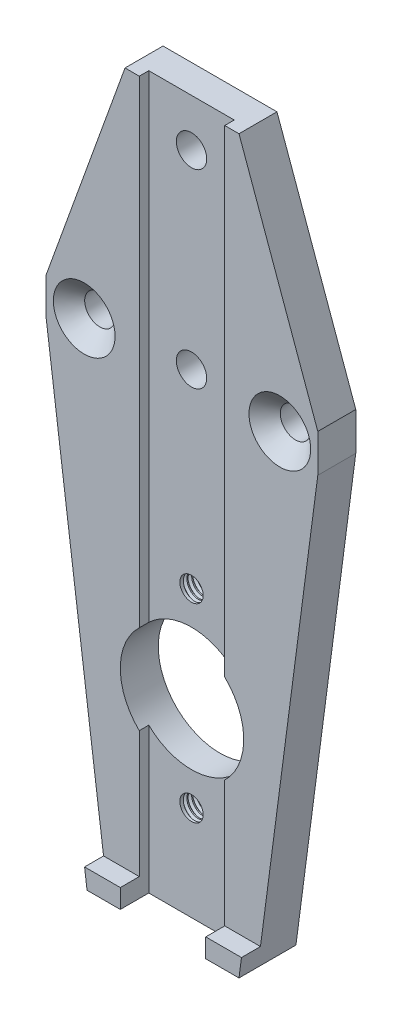
SolidWorks part; units mm, degrees
ref_plane "前视基准面" through (0, 0, 0) normal (0, 0, 1) x (1, 0, 0)
ref_plane "上视基准面" through (0, 0, 0) normal (0, 1, 0) x (1, 0, 0)
ref_plane "右视基准面" through (0, 0, 0) normal (1, 0, 0) x (0, 0, -1)
sketch "Model" plane through (0, 0, 0) normal (0, 0, 1) x (1, 0, 0)
  line L0 (-22.9666, -11.0807) -> (-22.9666, 4.2289)
  line L1 (-22.9666, -9.0807) -> (-26.7597, -9.0807)
  line L2 (-13.9666, -11.0807) -> (-13.9666, 4.2289)
  line L3 (-10.4666, -11.0807) -> (-26.4666, -11.0807)
  line L4 (-13.9666, -9.0807) -> (-10.1736, -9.0807)
  line L5 (-4.1666, 36.9193) -> (-4.1666, 40.9193)
  line L6 (-10.4666, -11.0807) -> (-4.1666, 36.9193)
  line L7 (-32.7666, 36.9193) -> (-32.7666, 40.9193)
  line L8 (-22.9666, 13.6097) -> (-22.9666, 63.9193)
  line L9 (-26.4666, -11.0807) -> (-32.7666, 36.9193)
  line L10 (-13.9666, 13.6097) -> (-13.9666, 63.9193)
  line L11 (-24.4666, 63.9193) -> (-12.4666, 63.9193)
  line L12 (-12.4666, 63.9193) -> (-4.1666, 40.9193)
  line L13 (-24.4666, 63.9193) -> (-32.7666, 40.9193)
  circle A0 centre (-18.4666, 8.9193) radius 6.5
  circle A1 centre (-8.1666, 38.9193) radius 1.6
  circle A2 centre (-18.4666, 38.9193) radius 1.6
  circle A3 centre (-28.7666, 38.9193) radius 1.6
  circle A4 centre (-18.4666, 58.9193) radius 1.6
  circle A5 centre (-8.1666, 38.9193) radius 3.25
  circle A6 centre (-28.7666, 38.9193) radius 3.25
  circle A7 centre (-18.4666, 18.9193) radius 1.2294
  arc A8 (-18.4666, 17.4193) -> (-19.9438, 18.6588) centre (-18.4666, 18.9193) ccw
  circle A9 centre (-18.4666, -1.0807) radius 1.2294
  arc A10 (-18.4666, -2.5807) -> (-19.9438, -1.3412) centre (-18.4666, -1.0807) ccw
extrude "凸台-拉伸1" add sketch "Model" along normal blind 3 contours A0 L10 L11 L8 A7 A4 A2 | A0 L0 L3 L2 A9 region at (-18.4666, -4.1536, 0) region at (-22.4556, 38.7645, 0)
extrude "凸台-拉伸2" add sketch "Model<3>" along normal blind 4 contours A0 L8 L11 L13 L7 L9 L1 L0 A6 | A0 L2 L4 L6 L5 L12 L11 L10 A5 | A6 A3 | A3 | A5 A1 | A1 | L9 L3 L0 L1 | L3 L6 L4 L2 region at (-24.783, -10.0687, 0) region at (-26.5297, 27.523, 0) region at (-12.1502, -10.0687, 0) region at (-10.4036, 27.523, 0) region at (-8.1666, 38.9193, 0) region at (-28.7666, 38.9193, 0) region at (-11.3247, 38.9193, 0) region at (-31.9247, 38.9193, 0)
sketch "Model<3>" plane through (0, 0, 0) normal (0, 0, 1) x (1, 0, 0) same geometry as "Model"
extrude "凸台-拉伸3" add sketch "Model<4>" along normal blind 6 contours L9 L3 L0 L1 | L3 L6 L4 L2 region at (-24.783, -10.0687, 0) region at (-12.1502, -10.0687, 0)
sketch "Model<4>" plane through (0, 0, 0) normal (0, 0, 1) x (1, 0, 0) same geometry as "Model"
sketch "草图2" plane through (0, 0, 4) normal (0, 0, 1) x (1, 0, 0)
  point P0 (-8.1666, 38.9193)
  point P2 (-28.7666, 38.9193)
hole_wizard "打孔尺寸(%根据)内六角花形半沉头螺钉的类型1" positions "3D草图1" profile "草图3" countersink size "M6" standard "GB" end condition up to next
sketch3d "3D草图1"
  point P0 (-28.7666, 38.9193, 4)
  point P3 (-8.1666, 38.9193, 4)
sketch "草图3" plane through (-28.7666, 38.9193, 4) normal (1, 0, 0) x (0, -1, 0)
  line L0 (0, 0) -> (0, 4)
  line L1 (0, 4) -> (1.6, 4)
  line L2 (1.6, 4) -> (1.6, 1.65)
  line L3 (1.6, 1.65) -> (3.25, 0)
  line L5 (3.25, 0) -> (0, 0)
  line L6 (-1.6, 1.65) -> (-3.25, 0) construction
  line L11 (0, -6.35) -> (0, 107.95) construction
  dimension "通孔孔直径" = 3.2
  dimension "通孔孔深度" = 4
  dimension "近端锥形沉头孔直径" = 6.5
  dimension "近端锥形沉头孔角度" = 90
thread "螺纹线4" pitch 0.5 method cut profile "螺纹线轮廓4" start angle 0, offset 0, length 0, pitch 0.5, diameter 2.4587
ref_plane "基准面7" through (-17.2373, 18.9193, 0) normal (0, -1, 0) x (1, 0, 0)
sketch "螺纹线轮廓4" plane through (-17.2373, 18.9193, 0) normal (0, -1, 0) x (1, 0, 0)
  line L0 (0, 0) -> (0, 0.5) construction
  line L1 (0, 0) -> (0.2706, 0.1562)
  line L2 (0.2706, 0.1562) -> (0.2706, 0.2187)
  line L3 (0.2706, 0.2187) -> (0, 0.375)
  line L4 (0.2706, 0.1875) -> (0, 0.1875) construction
  line L11 (0, 0) -> (0, 0.375)
  point P2 (0, 0)
  dimension "Pitch" = 0.5
  dimension "Profile_Angle" = 60
  dimension "Profile_Land" = 0.0625
  dimension "Profile_Height" = 0.2706
thread "螺纹线5" pitch 0.5 method cut profile "螺纹线轮廓5" start angle 0, offset 0, length 0, pitch 0.5, diameter 2.4587
ref_plane "基准面8" through (-17.2373, -1.0807, 0) normal (0, -1, 0) x (1, 0, 0)
sketch "螺纹线轮廓5" plane through (-17.2373, -1.0807, 0) normal (0, -1, 0) x (1, 0, 0)
  line L0 (0, 0) -> (0, 0.5) construction
  line L1 (0, 0) -> (0.2706, 0.1562)
  line L2 (0.2706, 0.1562) -> (0.2706, 0.2187)
  line L3 (0.2706, 0.2187) -> (0, 0.375)
  line L4 (0.2706, 0.1875) -> (0, 0.1875) construction
  line L11 (0, 0) -> (0, 0.375)
  point P2 (0, 0)
  dimension "Pitch" = 0.5
  dimension "Profile_Angle" = 60
  dimension "Profile_Land" = 0.0625
  dimension "Profile_Height" = 0.2706
